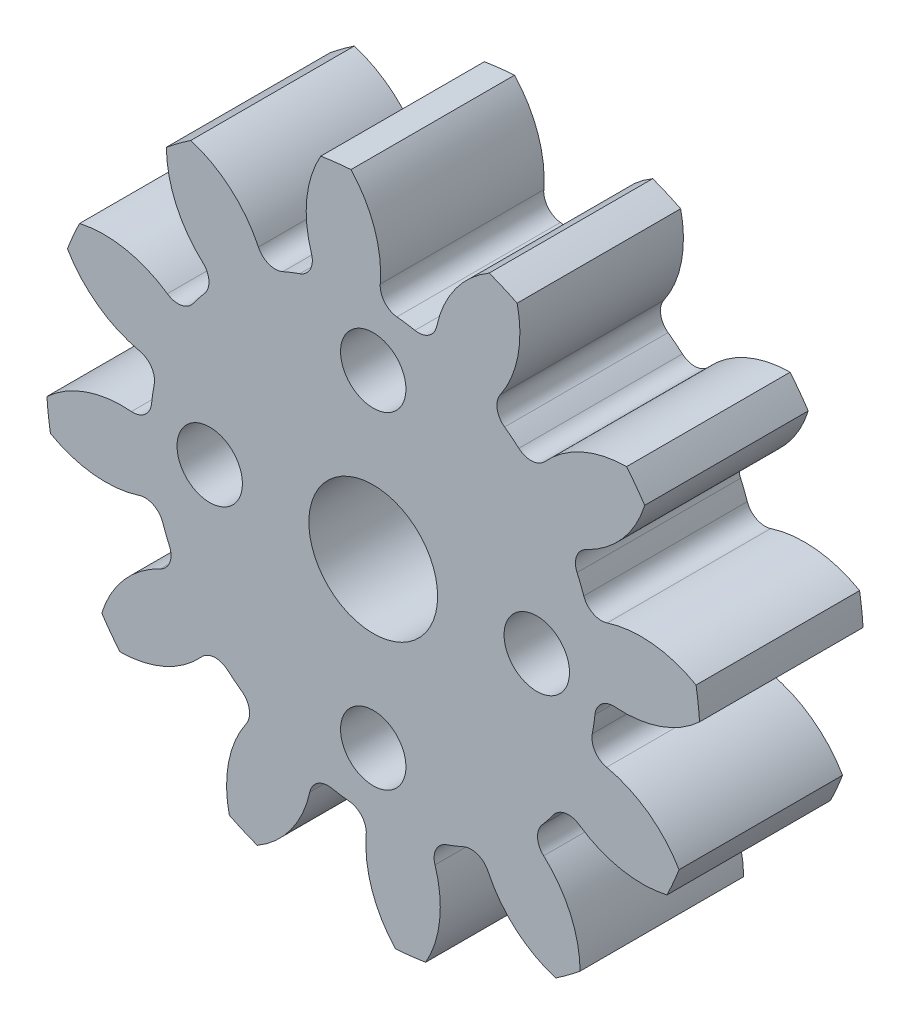
SolidWorks part; units mm, degrees
ref_plane "Front" through (0, 0, 0) normal (0, 0, 1) x (1, 0, 0)
ref_plane "Top" through (0, 0, 0) normal (0, 1, 0) x (1, 0, 0)
ref_plane "Right" through (0, 0, 0) normal (1, 0, 0) x (0, 0, -1)
sketch "Sketch3" plane through (0, 0, 0) normal (0, 0, 1) x (1, 0, 0)
  circle A0 centre (0, 0) radius 12.7
  dimension "od" = 25.4
extrude "gearBody" add sketch "Sketch3" along normal blind 6.35
sketch "Sketch2" plane through (0, 0, 0) normal (0, 0, 1) x (1, 0, 0)
  line L0 (0, 0) -> (9.7367, 4.0331) construction
  line L1 (12.2684, -5.3917) -> (0, 0) construction
  line L2 (0, 0) -> (36.3143, 0) construction
  line L3 (10.8849, -0.1309) -> (10.4544, -3.0337) construction
  line L5 (10.6697, -1.5823) -> (0, 0) construction
  line L7 (0, 0) -> (10.539, 0) construction
  arc A0 (10.5369, -0.2115) -> (10.1448, -2.8555) centre (0, 0) ccw construction
  arc A1 (12.6706, 0.8631) -> (11.8749, -4.5031) centre (0, 0) ccw construction
  arc A2 (10.8849, -0.1309) -> (10.4544, -3.0337) centre (0, 0) ccw construction
  arc A3 (8.505, -1.6194) -> (8.6089, -0.9186) centre (0, 0) ccw
  arc A4 (12.2684, -5.3917) -> (9.0639, -2.4643) centre (8.1472, -6.6852) ccw
  arc A5 (12.2684, -5.3917) -> (13.3051, 1.5993) centre (0, 0) ccw
  arc A6 (13.3051, 1.5993) -> (9.389, -0.2722) centre (9.7367, 4.0331) cw
  arc A7 (8.6089, -0.9186) -> (9.389, -0.2722) centre (9.3305, -0.9956) cw
  arc A8 (9.0639, -2.4643) -> (8.505, -1.6194) centre (9.2179, -1.7551) cw
  point P6 (13.3051, 1.5993)
  point P22 (12.2684, -5.3917)
  dimension "baseDia" = 21.078
  dimension "od" = 25.4
  dimension "pd" = 21.7714
  dimension "rd" = 17.3155
  dimension "rFillet" = 0.7257
  dimension "pointX" = 13.3051
  dimension "pointY" = 1.5993
  dimension "CTT" = 2.9029
  dimension "flankCenterAngle" = 22.5
extrude "toothCut" cut sketch "Sketch2" along normal through all
pattern_circular "CirPattern1" count 12 over 360 about axis through (0, 0, 6.35) along (0, 0, -1) of "toothCut"
ref_axis "toothSpace" through (0, 0, 0) along (0.9892, -0.1467, 0)
ref_axis "Axis2" through (11.6524, -5.051, 0) along (-0.9175, 0.3977, 0)
sketch "hub1Dia" plane through (0, 0, 0) normal (0, 0, -1) x (-1, 0, 0)
  circle A0 centre (0, 0) radius 12.7
  dimension "hub1Dia" = 25.4
sketch "hub2Dia" plane through (0, 0, 6.35) normal (0, 0, 1) x (1, 0, 0)
  circle A0 centre (0, 0) radius 12.7
  dimension "hub2dia" = 25.4
sketch "boreDia" plane through (0, 0, 0) normal (0, 0, 1) x (1, 0, 0)
  circle A0 centre (0, 0) radius 2.5
  circle A1 centre (0, 6.35) radius 1.27
  circle A2 centre (6.35, 0) radius 1.27
  circle A3 centre (-6.35, 0) radius 1.27
  circle A4 centre (0, -6.35) radius 1.27
  dimension "D1" = 2.54
  dimension "boreDia" = 5
  dimension "D2" = 2.54
  dimension "D3" = 2.54
  dimension "D4" = 2.54
  dimension "D5" = 6.35
  dimension "D6" = 6.35
  dimension "D7" = 6.35
  dimension "D8" = 6.35
extrude "bore" cut sketch "boreDia" against normal mid plane 25400
sketch "kwy1sketch" plane through (0, 0, 0) normal (0, 0, 1) x (1, 0, 0)
  line L0 (-5.8056, 1.9352) -> (0, 0) construction
  line L1 (30.4018, 3.2528) -> (22.3695, -20.8437)
  line L2 (22.3695, -20.8437) -> (-7.7511, -10.8032)
  line L3 (30.4018, 3.2528) -> (0.2812, 13.2933)
  line L4 (-7.7511, -10.8032) -> (0, 0)
  line L5 (0, 0) -> (0.2812, 13.2933)
  line L6 (0, 0) -> (8.5641, -1.27) construction
  line L7 (26.3857, -8.7954) -> (0, 0) construction
  arc A7 (8.505, -1.6194) -> (8.6089, -0.9186) centre (0, 0) ccw construction
  point P9 (26.3857, -8.7954)
  point P13 (-0.9684, 0.3228)
  dimension "kwy1width" = 25.4
  dimension "kwy1depth" = 27.813
  dimension "kwy1angle" = 10
  dimension "kwy1Depth2" = 31.75
sketch "kwy2sketch" plane through (0, 0, 0) normal (0, 0, 1) x (1, 0, 0)
  line L0 (8.5641, -1.27) -> (0, 0) construction
  line L1 (0, 0) -> (-3.7824, -1.8912) construction
  line L2 (19.1973, 23.7974) -> (30.5563, 1.0789)
  line L3 (30.5563, 1.0789) -> (2.1582, -13.1199)
  line L4 (19.1973, 23.7974) -> (-9.2009, 9.5986)
  line L5 (2.1582, -13.1199) -> (0, 0)
  line L6 (0, 0) -> (-9.2009, 9.5986)
  arc A2 (8.505, -1.6194) -> (8.6089, -0.9186) centre (0, 0) ccw construction
  point P10 (24.8768, 12.4382)
  dimension "kwy2angle" = 35
  dimension "kwy2Width" = 25.4
  dimension "kwy2depth" = 27.813
  dimension "kwy2Depth2" = 31.75
sketch "kwy3sketch" plane through (0, 0, 0) normal (0, 0, 1) x (1, 0, 0)
  line L0 (8.5641, -1.27) -> (0, 0) construction
  line L1 (0, 0) -> (-0.9675, -2.9024) construction
  line L2 (-3.2528, 30.4018) -> (20.8437, 22.3695)
  line L3 (20.8437, 22.3695) -> (10.8032, -7.7511)
  line L4 (-3.2528, 30.4018) -> (-13.2933, 0.2812)
  line L5 (10.8032, -7.7511) -> (0, 0)
  line L6 (-13.2933, 0.2812) -> (0, 0)
  point P10 (8.7954, 26.3857)
  dimension "kwy3angle" = 80
  dimension "kwy3depth" = 27.813
  dimension "kwy3width" = 25.4
  dimension "kwy3Depth2" = 31.75
sketch "kwy4sketch" plane through (0, 0, 0) normal (0, 0, 1) x (1, 0, 0)
  line L0 (8.5641, -1.27) -> (0, 0) construction
  line L1 (0, 0) -> (1.0698, -2.1396) construction
  line L2 (-1.0789, 30.5563) -> (-23.7974, 19.1973)
  line L3 (-23.7974, 19.1973) -> (-9.5986, -9.2009)
  line L4 (-9.5986, -9.2009) -> (0, 0)
  line L5 (13.1199, 2.1582) -> (0, 0)
  line L6 (-1.0789, 30.5563) -> (13.1199, 2.1582)
  point P15 (-12.4382, 24.8768)
  dimension "kwy4angle" = 125
  dimension "kwy4depth" = 27.813
  dimension "kwy4width" = 25.4
  dimension "kwy4Depth2" = 31.75
sketch "kwy5sketch" plane through (0, 0, 0) normal (0, 0, 1) x (1, 0, 0)
  line L0 (8.5641, -1.27) -> (0, 0) construction
  line L1 (0, 0) -> (1.949, -0.6497) construction
  line L2 (-22.3695, 20.8437) -> (-30.4018, -3.2528)
  line L3 (-30.4018, -3.2528) -> (-0.2812, -13.2933)
  line L4 (-22.3695, 20.8437) -> (7.7511, 10.8032)
  line L5 (-0.2812, -13.2933) -> (0, 0)
  line L6 (7.7511, 10.8032) -> (0, 0)
  point P10 (-26.3857, 8.7954)
  dimension "kwy5width" = 25.4
  dimension "kwy5depth" = 27.813
  dimension "kwy5angle" = 170
  dimension "kwy5Depth2" = 31.75
sketch "kwy6sketch" plane through (0, 0, 0) normal (0, 0, 1) x (1, 0, 0)
  line L0 (8.5641, -1.27) -> (0, 0) construction
  line L1 (0, 0) -> (1.8361, 0.918) construction
  line L2 (-30.5563, -1.0789) -> (-19.1973, -23.7974)
  line L3 (-19.1973, -23.7974) -> (9.2009, -9.5986)
  line L4 (-30.5563, -1.0789) -> (-2.1582, 13.1199)
  line L5 (9.2009, -9.5986) -> (0, 0)
  line L6 (-2.1582, 13.1199) -> (0, 0)
  point P10 (-24.8768, -12.4382)
  dimension "kwy6angle" = 215
  dimension "kwy6width" = 25.4
  dimension "kwy6depth" = 27.813
  dimension "kwy6Depth2" = 31.75
sketch "kwy7sketch" plane through (0, 0, 0) normal (0, 0, 1) x (1, 0, 0)
  line L0 (8.5641, -1.27) -> (0, 0) construction
  line L1 (0, 0) -> (0.7273, 2.1818) construction
  line L2 (-20.8437, -22.3695) -> (3.2528, -30.4018)
  line L3 (-20.8437, -22.3695) -> (-10.8032, 7.7511)
  line L4 (3.2528, -30.4018) -> (13.2933, -0.2812)
  line L5 (-10.8032, 7.7511) -> (0, 0)
  line L6 (13.2933, -0.2812) -> (0, 0)
  point P10 (-8.7954, -26.3857)
  dimension "kwy7angle" = 80
  dimension "kwy7width" = 25.4
  dimension "kwy7depth" = 27.813
  dimension "kwy7angle1" = 260
  dimension "kwy7Depth2" = 31.75
sketch "kwy8sketch" plane through (0, 0, 0) normal (0, 0, 1) x (1, 0, 0)
  line L0 (8.5641, -1.27) -> (0, 0) construction
  line L1 (0, 0) -> (-0.9138, 1.8276) construction
  line L2 (1.0789, -30.5563) -> (23.7974, -19.1973)
  line L3 (23.7974, -19.1973) -> (9.5986, 9.2009)
  line L4 (1.0789, -30.5563) -> (-13.1199, -2.1582)
  line L5 (9.5986, 9.2009) -> (0, 0)
  line L6 (-13.1199, -2.1582) -> (0, 0)
  point P10 (12.4382, -24.8768)
  dimension "kwy8angle" = 305
  dimension "kwy8width" = 25.4
  dimension "kwy8depth" = 27.813
  dimension "kwy8Depth2" = 31.75
sketch "centerLine" plane through (0, 0, 0) normal (0, 1, 0) x (1, 0, 0)
  line L0 (0, 36.4807) -> (0, -59.6309) construction
ref_plane "CB1plane" through (0, 0, 0) normal (0, 0, -1) x (-1, 0, 0)
sketch "CB1diameter" plane through (0, 0, 0) normal (0, 0, -1) x (-1, 0, 0)
  circle A0 centre (0, 0) radius 12.7
  dimension "CB1diameter" = 25.4
ref_plane "CB2plane" through (0, 0, 6.35) normal (0, 0, 1) x (1, 0, 0)
sketch "CB2diameter" plane through (0, 0, 6.35) normal (0, 0, 1) x (1, 0, 0)
  circle A0 centre (0, 0) radius 12.7
  dimension "CB2diameter" = 25.4
ref_axis "Axis1" through (0, 0, 50) along (0, 0, -1)
